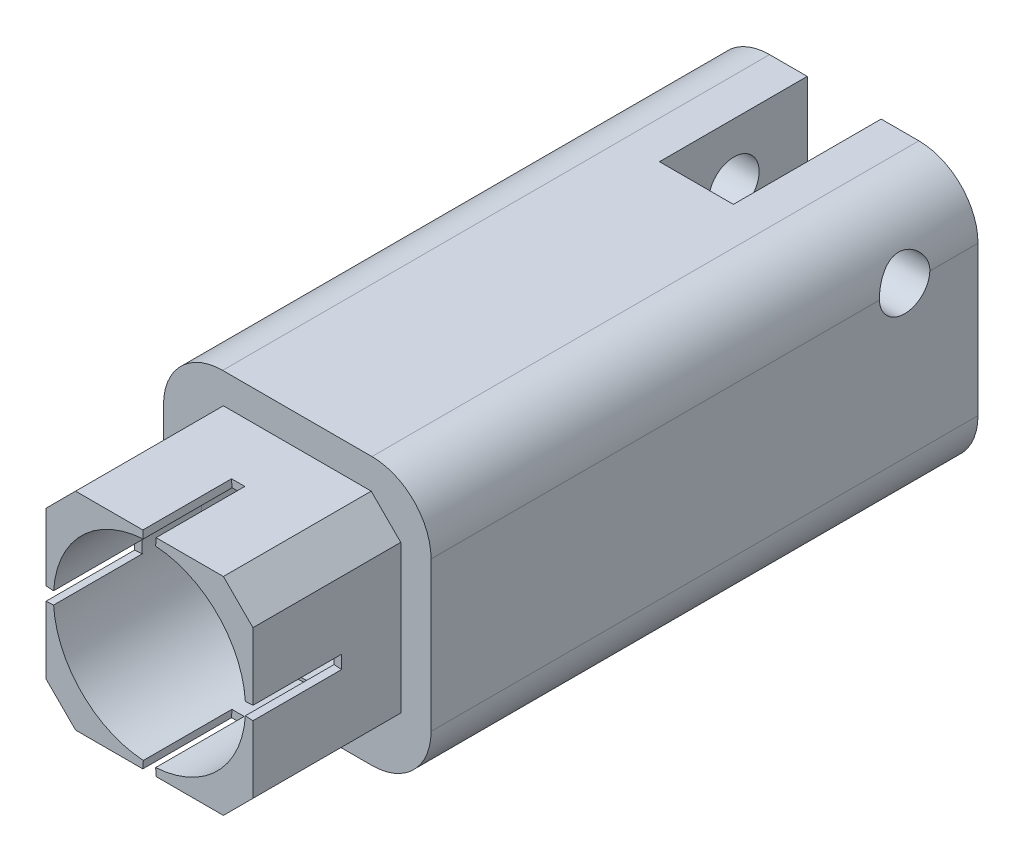
SolidWorks part; units mm, degrees
ref_plane "Front Plane" through (0, 0, 0) normal (0, 0, 1) x (1, 0, 0)
ref_plane "Top Plane" through (0, 0, 0) normal (0, 1, 0) x (1, 0, 0)
ref_plane "Right Plane" through (0, 0, 0) normal (1, 0, 0) x (0, 0, -1)
sketch "Sketch1" plane through (0, 0, 0) normal (0, 0, 1) x (1, 0, 0)
  line L0 (-5.05, 9.05) -> (5.05, 9.05)
  line L1 (9.05, -5.05) -> (9.05, 5.05)
  line L2 (0, 0) -> (0, 14.1446) construction
  line L3 (-9.05, -5.05) -> (-9.05, 5.05)
  line L4 (-12.732, 0) -> (15.0845, 0) construction
  line L5 (-5.05, -9.05) -> (5.05, -9.05)
  arc A4 (5.05, 9.05) -> (9.05, 5.05) centre (5.05, 5.05) cw
  arc A5 (9.05, -5.05) -> (5.05, -9.05) centre (5.05, -5.05) cw
  arc A6 (-5.05, -9.05) -> (-9.05, -5.05) centre (-5.05, -5.05) cw
  arc A7 (-9.05, 5.05) -> (-5.05, 9.05) centre (-5.05, 5.05) cw
  point P11 (9.05, 0)
  point P12 (0, 9.05)
  point P20 (0, -9.05)
  point P21 (-9.05, 0)
  dimension "D3" = 0
  dimension "D1" = 5.05
  dimension "D2" = 5.05
  dimension "D4" = 9.05
  dimension "D5" = 9.05
extrude "Boss-Extrude1" add sketch "Sketch1" along normal blind 37
sketch "Sketch3" plane through (0, 0, 37) normal (0, 0, 1) x (1, 0, 0)
  line L0 (-5, -7) -> (5, -7)
  line L1 (-7, -5) -> (-7, 5)
  line L2 (-5, 7) -> (5, 7)
  line L3 (7, -5) -> (7, 5)
  line L4 (-7, -7) -> (7, 7) construction
  line L5 (-7, 7) -> (7, -7) construction
  line L6 (-5, 7) -> (-7, 5)
  line L7 (5, 7) -> (7, 5)
  line L8 (7, -5) -> (5, -7)
  line L9 (-5, -7) -> (-7, -5)
  circle A6 centre (0, 0) radius 6.5
  point P3 (0, 0)
  dimension "D1" = 14
  dimension "D3" = 13
  dimension "D4" = 0
  dimension "D5" = 0
  dimension "D6" = 0
extrude "Boss-Extrude2" add sketch "Sketch3" along normal blind 10
sketch "Sketch11" plane through (0, 0, 47) normal (0, 0, 1) x (1, 0, 0)
  line L0 (0, 0) -> (7, 0.45)
  line L1 (7, -5) -> (7, 5) construction
  line L2 (7, 0.45) -> (7, -0.45)
  line L3 (7, -0.45) -> (0, 0)
  dimension "D1" = 0.45
  dimension "D2" = 0.45
extrude "Cut-Extrude7" cut sketch "Sketch11" against normal blind 6
pattern_circular "CirPattern1" count 4 over 360 about axis through (0, 0, 47) along (0, 0, -1) of "Cut-Extrude7" reverse direction yes
sketch "Sketch12" plane through (0, 0, 37) normal (0, 0, 1) x (1, 0, 0)
  line L0 (0, 0) -> (0, 14.1446) construction
  circle A0 centre (0, 0.1925) radius 6.5
  dimension "D1" = 13
extrude "Cut-Extrude8" cut sketch "Sketch12" against normal blind 25
sketch "Sketch13" plane through (0, 0, 0) normal (0, 0, 1) x (1, 0, 0)
  line L0 (-12.732, 0) -> (15.0845, 0) construction
  line L3 (-2.5, 0) -> (-2.5, 9.05)
  line L4 (-5.05, 9.05) -> (5.05, 9.05) construction
  line L5 (-2.5, 9.05) -> (2.5, 9.05)
  line L6 (2.5, 9.05) -> (2.5, 0)
  arc A0 (-2.5, 0) -> (2.5, 0) centre (0, 0) ccw
  dimension "D2" = 2.5
  dimension "D1" = 0
extrude "Cut-Extrude9" cut sketch "Sketch13" along normal blind 10
sketch "Sketch14" plane through (0, 0, 0) normal (1, 0, 0) x (0, 0, -1)
  circle A0 centre (-4.9636, 5.105) radius 1.705
  dimension "D1" = 3.41
  dimension "D2" = 5.105
extrude "Cut-Extrude10" cut sketch "Sketch14" against normal mid plane 25
